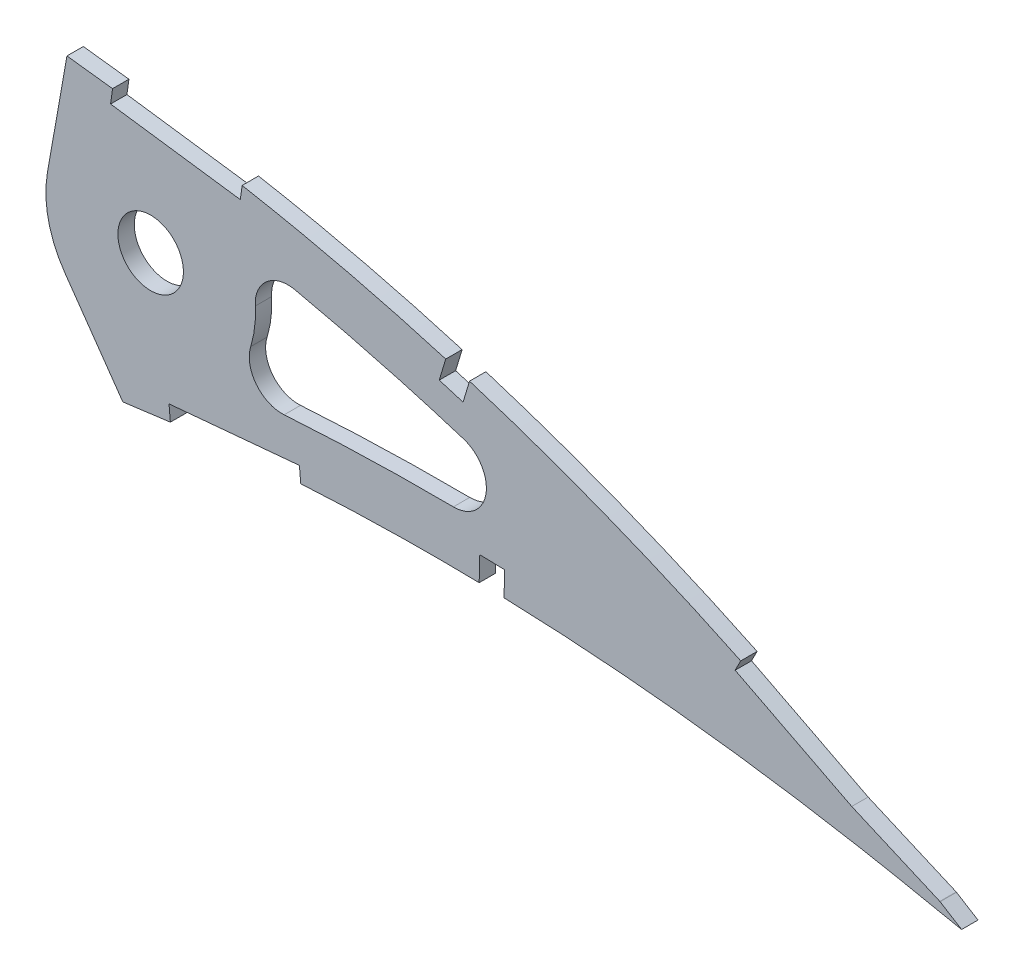
SolidWorks part; units mm, degrees
material "Plywood"
ref_plane "Front Plane" through (0, 0, 0) normal (0, 0, 1) x (1, 0, 0)
ref_plane "Top Plane" through (0, 0, 0) normal (0, 1, 0) x (1, 0, 0)
ref_plane "Right Plane" through (0, 0, 0) normal (1, 0, 0) x (0, 0, -1)
curve "Curve2"
  spline degree 3 poles (520.229, 0.8111, 0) (520.1892, 0.8357, 0) (520.0299, 0.9341, 0) (519.6711, 1.1542, 0) (519.0735, 1.5208, 0) (518.237, 2.0313, 0) (517.1622, 2.6844, 0) (515.8486, 3.4756, 0) (514.2969, 4.4021, 0) (512.5075, 5.4598, 0) (510.4807, 6.6436, 0) (508.2172, 7.9486, 0) (505.7172, 9.3676, 0) (502.9816, 10.8948, 0) (500.0114, 12.5227, 0) (496.8072, 14.2443, 0) (493.3701, 16.0505, 0) (489.7015, 17.9338, 0) (485.8019, 19.8836, 0) (481.6733, 21.8919, 0) (477.317, 23.9487, 0) (472.7345, 26.0429, 0) (467.9284, 28.1661, 0) (462.9001, 30.305, 0) (457.6524, 32.4505, 0) (452.1876, 34.5902, 0) (446.5089, 36.7144, 0) (440.6184, 38.8094, 0) (434.5207, 40.866, 0) (428.2186, 42.8708, 0) (421.7166, 44.813, 0) (415.0186, 46.68, 0) (408.1302, 48.4622, 0) (401.0555, 50.1466, 0) (393.8008, 51.7219, 0) (386.3718, 53.1787, 0) (378.7746, 54.5024, 0) (371.0303, 55.692, 0) (363.2636, 56.6815, 0) (355.5128, 57.652, 0) (347.7736, 58.5637, 0) (339.9398, 59.4368, 0) (332.019, 60.2663, 0) (324.019, 61.0497, 0) (315.9478, 61.7836, 0) (307.814, 62.4658, 0) (299.6253, 63.0925, 0) (291.3904, 63.6628, 0) (283.1174, 64.1714, 0) (274.8152, 64.6183, 0) (266.4922, 65.0001, 0) (258.157, 65.3142, 0) (249.8185, 65.5589, 0) (241.4854, 65.7316, 0) (233.1666, 65.8314, 0) (224.8708, 65.8555, 0) (216.6071, 65.8035, 0) (208.384, 65.6736, 0) (200.2107, 65.464, 0) (192.0958, 65.1743, 0) (184.048, 64.8046, 0) (176.0762, 64.3519, 0) (168.189, 63.8191, 0) (160.3952, 63.2038, 0) (152.7034, 62.506, 0) (145.1216, 61.7286, 0) (137.6583, 60.8693, 0) (130.3214, 59.9308, 0) (123.1191, 58.9147, 0) (116.0593, 57.8206, 0) (109.1496, 56.6517, 0) (102.3976, 55.409, 0) (95.8102, 54.0963, 0) (89.3948, 52.714, 0) (83.1581, 51.266, 0) (77.1065, 49.7551, 0) (71.2467, 48.1838, 0) (65.5845, 46.5561, 0) (60.1256, 44.8756, 0) (54.8764, 43.1442, 0) (49.8409, 41.3683, 0) (45.0253, 39.5493, 0) (40.4333, 37.6928, 0) (36.0702, 35.8014, 0) (31.9393, 33.8806, 0) (28.0452, 31.9329, 0) (24.3908, 29.9636, 0) (20.9797, 27.9757, 0) (17.8153, 25.973, 0) (14.8987, 23.9604, 0) (12.2341, 21.9394, 0) (9.8224, 19.9149, 0) (7.6651, 17.8901, 0) (5.7652, 15.8664, 0) (4.1228, 13.8473, 0) (2.7399, 11.8344, 0) (1.6168, 9.8297, 0) (0.7561, 7.8345, 0) (0.1568, 5.85, 0) (-0.1712, 3.8792, 0) (-0.2528, 1.9205, 0) (-0.0842, 0.6392, 0) (0, 0, 0) knots 0 0 0 0 0.000254 0.001015 0.002283 0.004057 0.006331 0.009105 0.012374 0.016134 0.02038 0.025106 0.030306 0.035972 0.0421 0.048678 0.055702 0.06316 0.071046 0.07935 0.088063 0.097176 0.106678 0.116562 0.126814 0.137428 0.148394 0.1597 0.171338 0.183298 0.19557 0.208144 0.221012 0.234162 0.247587 0.261277 0.275223 0.289414 0.303771 0.317689 0.331784 0.34604 0.360444 0.374983 0.38964 0.404403 0.419257 0.434187 0.449177 0.464215 0.479284 0.49437 0.509458 0.524532 0.539579 0.554583 0.56953 0.584403 0.599191 0.613877 0.628447 0.642889 0.657186 0.671326 0.685294 0.699078 0.712665 0.726043 0.739198 0.752118 0.764792 0.777208 0.789356 0.801224 0.812804 0.824083 0.835055 0.84571 0.856038 0.866034 0.875689 0.884998 0.893953 0.902553 0.910789 0.918661 0.926166 0.933303 0.940071 0.946475 0.952518 0.958205 0.963547 0.968557 0.97325 0.977651 0.981787 0.985694 0.989415 0.993001 0.996508 1 1 1 1
curve "Curve3"
  spline degree 3 poles (0, 0, 0) (0.1336, -0.6306, 0) (0.4014, -1.8948, 0) (1.129, -3.7148, 0) (2.0912, -5.4642, 0) (3.3081, -7.1386, 0) (4.7718, -8.7374, 0) (6.479, -10.2623, 0) (8.428, -11.7125, 0) (10.6162, -13.0874, 0) (13.0406, -14.3883, 0) (15.6982, -15.6145, 0) (18.5868, -16.7656, 0) (21.7032, -17.8401, 0) (25.0435, -18.8396, 0) (28.6046, -19.7616, 0) (32.3825, -20.6074, 0) (36.3735, -21.375, 0) (40.5732, -22.065, 0) (44.9774, -22.6771, 0) (49.5814, -23.2117, 0) (54.3808, -23.6676, 0) (59.3708, -24.0458, 0) (64.5464, -24.3466, 0) (69.9027, -24.5709, 0) (75.4344, -24.718, 0) (81.1363, -24.7899, 0) (87.003, -24.788, 0) (93.0289, -24.7115, 0) (99.2088, -24.5648, 0) (105.5368, -24.3469, 0) (112.0073, -24.0604, 0) (118.6142, -23.7083, 0) (125.3518, -23.2917, 0) (132.2141, -22.8125, 0) (139.1951, -22.2745, 0) (146.2885, -21.679, 0) (153.4882, -21.0296, 0) (160.7876, -20.3295, 0) (168.1806, -19.5808, 0) (175.6606, -18.7872, 0) (183.2209, -17.9512, 0) (190.8551, -17.0772, 0) (198.5563, -16.1668, 0) (206.3179, -15.2253, 0) (214.1326, -14.2544, 0) (221.9939, -13.2579, 0) (229.8947, -12.2404, 0) (237.8276, -11.2019, 0) (245.786, -10.1497, 0) (253.7621, -9.0829, 0) (261.7491, -8.0072, 0) (269.7395, -6.9257, 0) (277.7256, -5.8389, 0) (285.7003, -4.7513, 0) (293.6562, -3.6657, 0) (301.5856, -2.5824, 0) (309.4812, -1.5067, 0) (317.3352, -0.4385, 0) (325.1402, 0.6201, 0) (332.8888, 1.6659, 0) (340.5737, 2.6975, 0) (348.187, 3.7144, 0) (355.721, 4.7168, 0) (363.0553, 5.6745, 0) (370.1707, 6.6383, 0) (377.0913, 7.4284, 0) (383.9258, 8.1028, 0) (390.6811, 8.6557, 0) (397.3493, 9.0951, 0) (403.9227, 9.4241, 0) (410.3934, 9.6473, 0) (416.7532, 9.7713, 0) (422.9943, 9.7993, 0) (429.1081, 9.7402, 0) (435.0867, 9.5987, 0) (440.9216, 9.3813, 0) (446.6049, 9.0952, 0) (452.1283, 8.7483, 0) (457.4837, 8.3456, 0) (462.6634, 7.8966, 0) (467.6597, 7.4078, 0) (472.4647, 6.8849, 0) (477.0715, 6.3387, 0) (481.4727, 5.7729, 0) (485.6616, 5.1968, 0) (489.6316, 4.6162, 0) (493.3764, 4.0385, 0) (496.89, 3.4693, 0) (500.1667, 2.916, 0) (503.2016, 2.384, 0) (505.9892, 1.8782, 0) (508.5257, 1.4052, 0) (510.8062, 0.9673, 0) (512.8275, 0.5717, 0) (514.5859, 0.2202, 0) (516.0789, -0.0824, 0) (517.3037, -0.3347, 0) (518.2586, -0.5328, 0) (518.9417, -0.6767, 0) (519.3522, -0.7624, 0) (519.5346, -0.8013, 0) (519.5802, -0.8111, 0) knots 0 0 0 0 0.003638 0.007293 0.011028 0.014901 0.018963 0.023258 0.027821 0.032679 0.037853 0.043362 0.049215 0.055422 0.061989 0.068918 0.076211 0.083868 0.091887 0.100266 0.109 0.118085 0.127515 0.137285 0.147388 0.157816 0.168563 0.179619 0.190977 0.202627 0.21456 0.226767 0.239236 0.251959 0.264924 0.27812 0.291536 0.30516 0.318981 0.332985 0.347163 0.361499 0.375981 0.390597 0.405333 0.420175 0.43511 0.450124 0.465203 0.480333 0.495501 0.51069 0.525887 0.541078 0.556247 0.571382 0.586466 0.601485 0.616424 0.631269 0.646007 0.660621 0.675098 0.689423 0.703582 0.716908 0.730009 0.742952 0.755726 0.76832 0.780724 0.792927 0.804916 0.816679 0.828204 0.839475 0.850481 0.861208 0.871639 0.881763 0.891564 0.901027 0.910139 0.918884 0.927249 0.935221 0.942785 0.949928 0.956638 0.962904 0.968712 0.974054 0.978918 0.983297 0.98718 0.990561 0.993433 0.995791 0.99763 0.998946 0.999737 1 1 1 1
sketch "Sketch1" plane through (0, 0, 0) normal (0, 0, 1) x (1, 0, 0)
  line L1 (519.5802, -0.8111) -> (524.4049, -1.7687)
  line L2 (520.229, 0.8111) -> (524.4049, -1.7687)
  spline S0 degree 3 poles (-2903.7635, -749.124) (66.2436, 68.8235) (-8.6937, 20.855) (1.129, -3.7148) (2.0912, -5.4642) (3.3081, -7.1386) (4.7718, -8.7374) (6.479, -10.2623) (8.428, -11.7125) (10.6162, -13.0874) (13.0406, -14.3883) (15.6982, -15.6145) (18.5868, -16.7656) (21.7032, -17.8401) (25.0435, -18.8396) (28.6046, -19.7616) (32.3825, -20.6074) (36.3735, -21.375) (40.5732, -22.065) (44.9774, -22.6771) (49.5814, -23.2117) (54.3808, -23.6676) (59.3708, -24.0458) (64.5464, -24.3466) (69.9027, -24.5709) (75.4344, -24.718) (81.1363, -24.7899) (87.003, -24.788) (93.0289, -24.7115) (99.2088, -24.5648) (105.5368, -24.3469) (112.0073, -24.0604) (118.6142, -23.7083) (125.3518, -23.2917) (132.2141, -22.8125) (139.1951, -22.2745) (146.2885, -21.679) (153.4882, -21.0296) (160.7876, -20.3295) (168.1806, -19.5808) (175.6606, -18.7872) (183.2209, -17.9512) (190.8551, -17.0772) (198.5563, -16.1668) (206.3179, -15.2253) (214.1326, -14.2544) (221.9939, -13.2579) (229.8947, -12.2404) (237.8276, -11.2019) (245.786, -10.1497) (253.7621, -9.0829) (261.7491, -8.0072) (269.7395, -6.9257) (277.7256, -5.8389) (285.7003, -4.7513) (293.6562, -3.6657) (301.5856, -2.5824) (309.4812, -1.5067) (317.3352, -0.4385) (325.1402, 0.6201) (332.8888, 1.6659) (340.5737, 2.6975) (348.187, 3.7144) (355.721, 4.7168) (363.0553, 5.6745) (370.1707, 6.6383) (377.0913, 7.4284) (383.9258, 8.1028) (390.6811, 8.6557) (397.3493, 9.0951) (403.9227, 9.4241) (410.3934, 9.6473) (416.7532, 9.7713) (422.9943, 9.7993) (429.1081, 9.7402) (435.0867, 9.5987) (440.9216, 9.3813) (446.6049, 9.0952) (452.1283, 8.7483) (457.4837, 8.3456) (462.6634, 7.8966) (467.6597, 7.4078) (472.4647, 6.8849) (477.0715, 6.3387) (481.4727, 5.7729) (485.6616, 5.1968) (489.6316, 4.6162) (493.3764, 4.0385) (496.89, 3.4693) (500.1667, 2.916) (503.2016, 2.384) (505.9892, 1.8782) (508.5257, 1.4052) (510.8062, 0.9673) (512.8275, 0.5717) (514.5859, 0.2202) (516.0789, -0.0824) (517.3037, -0.3347) (518.2586, -0.5328) (518.9417, -0.6767) (537.0698, -4.4604) (553.3394, -15.9066) (1193.1482, 2921.6684) knots -0.137857 -0.137857 -0.137857 -0.137857 0.003638 0.007293 0.011028 0.014901 0.018963 0.023258 0.027821 0.032679 0.037853 0.043362 0.049215 0.055422 0.061989 0.068918 0.076211 0.083868 0.091887 0.100266 0.109 0.118085 0.127515 0.137285 0.147388 0.157816 0.168563 0.179619 0.190977 0.202627 0.21456 0.226767 0.239236 0.251959 0.264924 0.27812 0.291536 0.30516 0.318981 0.332985 0.347163 0.361499 0.375981 0.390597 0.405333 0.420175 0.43511 0.450124 0.465203 0.480333 0.495501 0.51069 0.525887 0.541078 0.556247 0.571382 0.586466 0.601485 0.616424 0.631269 0.646007 0.660621 0.675098 0.689423 0.703582 0.716908 0.730009 0.742952 0.755726 0.76832 0.780724 0.792927 0.804916 0.816679 0.828204 0.839475 0.850481 0.861208 0.871639 0.881763 0.891564 0.901027 0.910139 0.918884 0.927249 0.935221 0.942785 0.949928 0.956638 0.962904 0.968712 0.974054 0.978918 0.983297 0.98718 0.990561 0.993433 0.995791 0.99763 0.998946 0.999737 1.102307 1.102307 1.102307 1.102307 only from (0, 0) to (519.5802, -0.8111) construction
  spline S1 degree 3 poles (2144.5607, 2521.6799) (550.9976, -26.3511) (537.2872, -9.6513) (519.6711, 1.1542) (519.0735, 1.5208) (518.237, 2.0313) (517.1622, 2.6844) (515.8486, 3.4756) (514.2969, 4.4021) (512.5075, 5.4598) (510.4807, 6.6436) (508.2172, 7.9486) (505.7172, 9.3676) (502.9816, 10.8948) (500.0114, 12.5227) (496.8072, 14.2443) (493.3701, 16.0505) (489.7015, 17.9338) (485.8019, 19.8836) (481.6733, 21.8919) (477.317, 23.9487) (472.7345, 26.0429) (467.9284, 28.1661) (462.9001, 30.305) (457.6524, 32.4505) (452.1876, 34.5902) (446.5089, 36.7144) (440.6184, 38.8094) (434.5207, 40.866) (428.2186, 42.8708) (421.7166, 44.813) (415.0186, 46.68) (408.1302, 48.4622) (401.0555, 50.1466) (393.8008, 51.7219) (386.3718, 53.1787) (378.7746, 54.5024) (371.0303, 55.692) (363.2636, 56.6815) (355.5128, 57.652) (347.7736, 58.5637) (339.9398, 59.4368) (332.019, 60.2663) (324.019, 61.0497) (315.9478, 61.7836) (307.814, 62.4658) (299.6253, 63.0925) (291.3904, 63.6628) (283.1174, 64.1714) (274.8152, 64.6183) (266.4922, 65.0001) (258.157, 65.3142) (249.8185, 65.5589) (241.4854, 65.7316) (233.1666, 65.8314) (224.8708, 65.8555) (216.6071, 65.8035) (208.384, 65.6736) (200.2107, 65.464) (192.0958, 65.1743) (184.048, 64.8046) (176.0762, 64.3519) (168.189, 63.8191) (160.3952, 63.2038) (152.7034, 62.506) (145.1216, 61.7286) (137.6583, 60.8693) (130.3214, 59.9308) (123.1191, 58.9147) (116.0593, 57.8206) (109.1496, 56.6517) (102.3976, 55.409) (95.8102, 54.0963) (89.3948, 52.714) (83.1581, 51.266) (77.1065, 49.7551) (71.2467, 48.1838) (65.5845, 46.5561) (60.1256, 44.8756) (54.8764, 43.1442) (49.8409, 41.3683) (45.0253, 39.5493) (40.4333, 37.6928) (36.0702, 35.8014) (31.9393, 33.8806) (28.0452, 31.9329) (24.3908, 29.9636) (20.9797, 27.9757) (17.8153, 25.973) (14.8987, 23.9604) (12.2341, 21.9394) (9.8224, 19.9149) (7.6651, 17.8901) (5.7652, 15.8664) (4.1228, 13.8473) (2.7399, 11.8344) (1.6168, 9.8297) (0.7561, 7.8345) (0.1568, 5.85) (-0.1712, 3.8792) (-1.2714, -22.5145) (85.5395, -42.7616) (-2987.8188, -259.5241) knots -0.109813 -0.109813 -0.109813 -0.109813 0.000254 0.001015 0.002283 0.004057 0.006331 0.009105 0.012374 0.016134 0.02038 0.025106 0.030306 0.035972 0.0421 0.048678 0.055702 0.06316 0.071046 0.07935 0.088063 0.097176 0.106678 0.116562 0.126814 0.137428 0.148394 0.1597 0.171338 0.183298 0.19557 0.208144 0.221012 0.234162 0.247587 0.261277 0.275223 0.289414 0.303771 0.317689 0.331784 0.34604 0.360444 0.374983 0.38964 0.404403 0.419257 0.434187 0.449177 0.464215 0.479284 0.49437 0.509458 0.524532 0.539579 0.554583 0.56953 0.584403 0.599191 0.613877 0.628447 0.642889 0.657186 0.671326 0.685294 0.699078 0.712665 0.726043 0.739198 0.752118 0.764792 0.777208 0.789356 0.801224 0.812804 0.824083 0.835055 0.84571 0.856038 0.866034 0.875689 0.884998 0.893953 0.902553 0.910789 0.918661 0.926166 0.933303 0.940071 0.946475 0.952518 0.958205 0.963547 0.968557 0.97325 0.977651 0.981787 0.985694 0.989415 0.993001 0.996508 1.132043 1.132043 1.132043 1.132043 only from (520.229, 0.8111) to (0, 0) construction
  spline S2 degree 3 poles (0, 0) (0.1336, -0.6306) (0.4014, -1.8948) (1.129, -3.7148) (2.0912, -5.4642) (3.3081, -7.1386) (4.7718, -8.7374) (6.479, -10.2623) (8.428, -11.7125) (10.6162, -13.0874) (13.0406, -14.3883) (15.6982, -15.6145) (18.5868, -16.7656) (21.7032, -17.8401) (25.0435, -18.8396) (28.6046, -19.7616) (32.3825, -20.6074) (36.3735, -21.375) (40.5732, -22.065) (44.9774, -22.6771) (49.5814, -23.2117) (54.3808, -23.6676) (59.3708, -24.0458) (64.5464, -24.3466) (69.9027, -24.5709) (75.4344, -24.718) (81.1363, -24.7899) (87.003, -24.788) (93.0289, -24.7115) (99.2088, -24.5648) (105.5368, -24.3469) (112.0073, -24.0604) (118.6142, -23.7083) (125.3518, -23.2917) (132.2141, -22.8125) (139.1951, -22.2745) (146.2885, -21.679) (153.4882, -21.0296) (160.7876, -20.3295) (168.1806, -19.5808) (175.6606, -18.7872) (183.2209, -17.9512) (190.8551, -17.0772) (198.5563, -16.1668) (206.3179, -15.2253) (214.1326, -14.2544) (221.9939, -13.2579) (229.8947, -12.2404) (237.8276, -11.2019) (245.786, -10.1497) (253.7621, -9.0829) (261.7491, -8.0072) (269.7395, -6.9257) (277.7256, -5.8389) (285.7003, -4.7513) (293.6562, -3.6657) (301.5856, -2.5824) (309.4812, -1.5067) (317.3352, -0.4385) (325.1402, 0.6201) (332.8888, 1.6659) (340.5737, 2.6975) (348.187, 3.7144) (355.721, 4.7168) (363.0553, 5.6745) (370.1707, 6.6383) (377.0913, 7.4284) (383.9258, 8.1028) (390.6811, 8.6557) (397.3493, 9.0951) (403.9227, 9.4241) (410.3934, 9.6473) (416.7532, 9.7713) (422.9943, 9.7993) (429.1081, 9.7402) (435.0867, 9.5987) (440.9216, 9.3813) (446.6049, 9.0952) (452.1283, 8.7483) (457.4837, 8.3456) (462.6634, 7.8966) (467.6597, 7.4078) (472.4647, 6.8849) (477.0715, 6.3387) (481.4727, 5.7729) (485.6616, 5.1968) (489.6316, 4.6162) (493.3764, 4.0385) (496.89, 3.4693) (500.1667, 2.916) (503.2016, 2.384) (505.9892, 1.8782) (508.5257, 1.4052) (510.8062, 0.9673) (512.8275, 0.5717) (514.5859, 0.2202) (516.0789, -0.0824) (517.3037, -0.3347) (518.2586, -0.5328) (518.9417, -0.6767) (519.3522, -0.7624) (519.5346, -0.8013) (519.5802, -0.8111) knots 0 0 0 0 0.003638 0.007293 0.011028 0.014901 0.018963 0.023258 0.027821 0.032679 0.037853 0.043362 0.049215 0.055422 0.061989 0.068918 0.076211 0.083868 0.091887 0.100266 0.109 0.118085 0.127515 0.137285 0.147388 0.157816 0.168563 0.179619 0.190977 0.202627 0.21456 0.226767 0.239236 0.251959 0.264924 0.27812 0.291536 0.30516 0.318981 0.332985 0.347163 0.361499 0.375981 0.390597 0.405333 0.420175 0.43511 0.450124 0.465203 0.480333 0.495501 0.51069 0.525887 0.541078 0.556247 0.571382 0.586466 0.601485 0.616424 0.631269 0.646007 0.660621 0.675098 0.689423 0.703582 0.716908 0.730009 0.742952 0.755726 0.76832 0.780724 0.792927 0.804916 0.816679 0.828204 0.839475 0.850481 0.861208 0.871639 0.881763 0.891564 0.901027 0.910139 0.918884 0.927249 0.935221 0.942785 0.949928 0.956638 0.962904 0.968712 0.974054 0.978918 0.983297 0.98718 0.990561 0.993433 0.995791 0.99763 0.998946 0.999737 1 1 1 1
  spline S3 degree 3 poles (520.229, 0.8111) (520.1892, 0.8357) (520.0299, 0.9341) (519.6711, 1.1542) (519.0735, 1.5208) (518.237, 2.0313) (517.1622, 2.6844) (515.8486, 3.4756) (514.2969, 4.4021) (512.5075, 5.4598) (510.4807, 6.6436) (508.2172, 7.9486) (505.7172, 9.3676) (502.9816, 10.8948) (500.0114, 12.5227) (496.8072, 14.2443) (493.3701, 16.0505) (489.7015, 17.9338) (485.8019, 19.8836) (481.6733, 21.8919) (477.317, 23.9487) (472.7345, 26.0429) (467.9284, 28.1661) (462.9001, 30.305) (457.6524, 32.4505) (452.1876, 34.5902) (446.5089, 36.7144) (440.6184, 38.8094) (434.5207, 40.866) (428.2186, 42.8708) (421.7166, 44.813) (415.0186, 46.68) (408.1302, 48.4622) (401.0555, 50.1466) (393.8008, 51.7219) (386.3718, 53.1787) (378.7746, 54.5024) (371.0303, 55.692) (363.2636, 56.6815) (355.5128, 57.652) (347.7736, 58.5637) (339.9398, 59.4368) (332.019, 60.2663) (324.019, 61.0497) (315.9478, 61.7836) (307.814, 62.4658) (299.6253, 63.0925) (291.3904, 63.6628) (283.1174, 64.1714) (274.8152, 64.6183) (266.4922, 65.0001) (258.157, 65.3142) (249.8185, 65.5589) (241.4854, 65.7316) (233.1666, 65.8314) (224.8708, 65.8555) (216.6071, 65.8035) (208.384, 65.6736) (200.2107, 65.464) (192.0958, 65.1743) (184.048, 64.8046) (176.0762, 64.3519) (168.189, 63.8191) (160.3952, 63.2038) (152.7034, 62.506) (145.1216, 61.7286) (137.6583, 60.8693) (130.3214, 59.9308) (123.1191, 58.9147) (116.0593, 57.8206) (109.1496, 56.6517) (102.3976, 55.409) (95.8102, 54.0963) (89.3948, 52.714) (83.1581, 51.266) (77.1065, 49.7551) (71.2467, 48.1838) (65.5845, 46.5561) (60.1256, 44.8756) (54.8764, 43.1442) (49.8409, 41.3683) (45.0253, 39.5493) (40.4333, 37.6928) (36.0702, 35.8014) (31.9393, 33.8806) (28.0452, 31.9329) (24.3908, 29.9636) (20.9797, 27.9757) (17.8153, 25.973) (14.8987, 23.9604) (12.2341, 21.9394) (9.8224, 19.9149) (7.6651, 17.8901) (5.7652, 15.8664) (4.1228, 13.8473) (2.7399, 11.8344) (1.6168, 9.8297) (0.7561, 7.8345) (0.1568, 5.85) (-0.1712, 3.8792) (-0.2528, 1.9205) (-0.0842, 0.6392) (0, 0) knots 0 0 0 0 0.000254 0.001015 0.002283 0.004057 0.006331 0.009105 0.012374 0.016134 0.02038 0.025106 0.030306 0.035972 0.0421 0.048678 0.055702 0.06316 0.071046 0.07935 0.088063 0.097176 0.106678 0.116562 0.126814 0.137428 0.148394 0.1597 0.171338 0.183298 0.19557 0.208144 0.221012 0.234162 0.247587 0.261277 0.275223 0.289414 0.303771 0.317689 0.331784 0.34604 0.360444 0.374983 0.38964 0.404403 0.419257 0.434187 0.449177 0.464215 0.479284 0.49437 0.509458 0.524532 0.539579 0.554583 0.56953 0.584403 0.599191 0.613877 0.628447 0.642889 0.657186 0.671326 0.685294 0.699078 0.712665 0.726043 0.739198 0.752118 0.764792 0.777208 0.789356 0.801224 0.812804 0.824083 0.835055 0.84571 0.856038 0.866034 0.875689 0.884998 0.893953 0.902553 0.910789 0.918661 0.926166 0.933303 0.940071 0.946475 0.952518 0.958205 0.963547 0.968557 0.97325 0.977651 0.981787 0.985694 0.989415 0.993001 0.996508 1 1 1 1
extrude "Boss-Extrude1" add sketch "Sketch1" along normal blind 3.175
sketch "Sketch4" plane through (0, 0, 0) normal (0, 0, -1) x (-1, 0, 0)
  line L0 (-347.1309, 36.7611) -> (-350.9097, 58.1919)
  line L1 (-350.497, 21.5775) -> (-361.7496, 5.5072)
  line L2 (-520.229, 0.8111) -> (-524.4049, -1.7687)
  line L3 (-524.4049, -1.7687) -> (-519.5802, -0.8111)
  line L6 (-367.1422, 33.2326) -> (-394.958, 33.2326)
  circle A0 centre (-367.1422, 33.2326) radius 20.32
  circle A1 centre (-367.1422, 33.2326) radius 6.35
  spline S0 degree 1 poles (-521.6997, 9.1254) (-10.022, 1.7185) knots 0 0 1 1 construction
  spline S1 degree 1 poles (-10.022, 1.7185) (-514.8893, -7.8326) knots 0 0 1 1 construction
  spline S2 degree 3 poles (2987.4901, -259.5009) (-85.5334, -42.7602) (1.2713, -22.5136) (0.1712, 3.8792) (-0.1568, 5.85) (-0.7561, 7.8345) (-1.6168, 9.8297) (-2.7399, 11.8344) (-4.1228, 13.8473) (-5.7652, 15.8664) (-7.6651, 17.8901) (-9.8224, 19.9149) (-12.2341, 21.9394) (-14.8987, 23.9604) (-17.8153, 25.973) (-20.9797, 27.9757) (-24.3908, 29.9636) (-28.0452, 31.9329) (-31.9393, 33.8806) (-36.0702, 35.8014) (-40.4333, 37.6928) (-45.0253, 39.5493) (-49.8409, 41.3683) (-54.8764, 43.1442) (-60.1256, 44.8756) (-65.5845, 46.5561) (-71.2467, 48.1838) (-77.1065, 49.7551) (-83.1581, 51.266) (-89.3948, 52.714) (-95.8102, 54.0963) (-102.3976, 55.409) (-109.1496, 56.6517) (-116.0593, 57.8206) (-123.1191, 58.9147) (-130.3214, 59.9308) (-137.6583, 60.8693) (-145.1216, 61.7286) (-152.7034, 62.506) (-160.3952, 63.2038) (-168.189, 63.8191) (-176.0762, 64.3519) (-184.048, 64.8046) (-192.0958, 65.1743) (-200.2107, 65.464) (-208.384, 65.6736) (-216.6071, 65.8035) (-224.8708, 65.8555) (-233.1666, 65.8314) (-241.4854, 65.7316) (-249.8185, 65.5589) (-258.157, 65.3142) (-266.4922, 65.0001) (-274.8152, 64.6183) (-283.1174, 64.1714) (-291.3904, 63.6628) (-299.6253, 63.0925) (-307.814, 62.4658) (-315.9478, 61.7836) (-324.019, 61.0497) (-332.019, 60.2663) (-339.9398, 59.4368) (-347.7736, 58.5637) (-355.5128, 57.652) (-363.2636, 56.6815) (-371.0303, 55.692) (-378.7746, 54.5024) (-386.3718, 53.1787) (-393.8008, 51.7219) (-401.0555, 50.1466) (-408.1302, 48.4622) (-415.0186, 46.68) (-421.7166, 44.813) (-428.2186, 42.8708) (-434.5207, 40.866) (-440.6184, 38.8094) (-446.5089, 36.7144) (-452.1876, 34.5902) (-457.6524, 32.4505) (-462.9001, 30.305) (-467.9284, 28.1661) (-472.7345, 26.0429) (-477.317, 23.9487) (-481.6733, 21.8919) (-485.8019, 19.8836) (-489.7015, 17.9338) (-493.3701, 16.0505) (-496.8072, 14.2443) (-500.0114, 12.5227) (-502.9816, 10.8948) (-505.7172, 9.3676) (-508.2172, 7.9486) (-510.4807, 6.6436) (-512.5075, 5.4598) (-514.2969, 4.4021) (-515.8486, 3.4756) (-517.1622, 2.6844) (-518.237, 2.0313) (-519.0735, 1.5208) (-519.6711, 1.1542) (-537.2876, -9.6516) (-550.9983, -26.352) (-2144.6851, 2521.8788) knots -0.132038 -0.132038 -0.132038 -0.132038 0.003492 0.006999 0.010585 0.014306 0.018213 0.022349 0.02675 0.031443 0.036453 0.041795 0.047482 0.053525 0.059929 0.066697 0.073834 0.081339 0.089211 0.097447 0.106047 0.115002 0.124311 0.133966 0.143962 0.15429 0.164945 0.175917 0.187196 0.198776 0.210644 0.222792 0.235208 0.247882 0.260802 0.273957 0.287335 0.300922 0.314706 0.328674 0.342814 0.357111 0.371553 0.386123 0.400809 0.415597 0.43047 0.445417 0.460421 0.475468 0.490542 0.50563 0.520716 0.535785 0.550823 0.565813 0.580743 0.595597 0.61036 0.625017 0.639556 0.65396 0.668216 0.682311 0.696229 0.710586 0.724777 0.738723 0.752413 0.765838 0.778988 0.791856 0.80443 0.816702 0.828662 0.8403 0.851606 0.862572 0.873186 0.883438 0.893322 0.902824 0.911937 0.92065 0.928954 0.93684 0.944298 0.951322 0.9579 0.964028 0.969694 0.974894 0.97962 0.983866 0.987626 0.990895 0.993669 0.995943 0.997717 0.998985 0.999746 1.109816 1.109816 1.109816 1.109816 only from (0, 0) to (-520.229, 0.8111)
  spline S3 degree 3 poles (-1193.1472, 2921.6638) (-553.3393, -15.9066) (-537.0698, -4.4604) (-518.9417, -0.6767) (-518.2586, -0.5328) (-517.3037, -0.3347) (-516.0789, -0.0824) (-514.5859, 0.2202) (-512.8275, 0.5717) (-510.8062, 0.9673) (-508.5257, 1.4052) (-505.9892, 1.8782) (-503.2016, 2.384) (-500.1667, 2.916) (-496.89, 3.4693) (-493.3764, 4.0385) (-489.6316, 4.6162) (-485.6616, 5.1968) (-481.4727, 5.7729) (-477.0715, 6.3387) (-472.4647, 6.8849) (-467.6597, 7.4078) (-462.6634, 7.8966) (-457.4837, 8.3456) (-452.1283, 8.7483) (-446.6049, 9.0952) (-440.9216, 9.3813) (-435.0867, 9.5987) (-429.1081, 9.7402) (-422.9943, 9.7993) (-416.7532, 9.7713) (-410.3934, 9.6473) (-403.9227, 9.4241) (-397.3493, 9.0951) (-390.6811, 8.6557) (-383.9258, 8.1028) (-377.0913, 7.4284) (-370.1707, 6.6383) (-363.0553, 5.6745) (-355.721, 4.7168) (-348.187, 3.7144) (-340.5737, 2.6975) (-332.8888, 1.6659) (-325.1402, 0.6201) (-317.3352, -0.4385) (-309.4812, -1.5067) (-301.5856, -2.5824) (-293.6562, -3.6657) (-285.7003, -4.7513) (-277.7256, -5.8389) (-269.7395, -6.9257) (-261.7491, -8.0072) (-253.7621, -9.0829) (-245.786, -10.1497) (-237.8276, -11.2019) (-229.8947, -12.2404) (-221.9939, -13.2579) (-214.1326, -14.2544) (-206.3179, -15.2253) (-198.5563, -16.1668) (-190.8551, -17.0772) (-183.2209, -17.9512) (-175.6606, -18.7872) (-168.1806, -19.5808) (-160.7876, -20.3295) (-153.4882, -21.0296) (-146.2885, -21.679) (-139.1951, -22.2745) (-132.2141, -22.8125) (-125.3518, -23.2917) (-118.6142, -23.7083) (-112.0073, -24.0604) (-105.5368, -24.3469) (-99.2088, -24.5648) (-93.0289, -24.7115) (-87.003, -24.788) (-81.1363, -24.7899) (-75.4344, -24.718) (-69.9027, -24.5709) (-64.5464, -24.3466) (-59.3708, -24.0458) (-54.3808, -23.6676) (-49.5814, -23.2117) (-44.9774, -22.6771) (-40.5732, -22.065) (-36.3735, -21.375) (-32.3825, -20.6074) (-28.6046, -19.7616) (-25.0435, -18.8396) (-21.7032, -17.8401) (-18.5868, -16.7656) (-15.6982, -15.6145) (-13.0406, -14.3883) (-10.6162, -13.0874) (-8.428, -11.7125) (-6.479, -10.2623) (-4.7718, -8.7374) (-3.3081, -7.1386) (-2.0912, -5.4642) (-1.129, -3.7148) (8.6936, 20.8547) (-66.2416, 68.8223) (2903.6435, -749.0909) knots -0.102307 -0.102307 -0.102307 -0.102307 0.000263 0.001054 0.00237 0.004209 0.006567 0.009439 0.01282 0.016703 0.021082 0.025946 0.031288 0.037096 0.043362 0.050072 0.057215 0.064779 0.072751 0.081116 0.089861 0.098973 0.108436 0.118237 0.128361 0.138792 0.149519 0.160525 0.171796 0.183321 0.195084 0.207073 0.219276 0.23168 0.244274 0.257048 0.269991 0.283092 0.296418 0.310577 0.324902 0.339379 0.353993 0.368731 0.383576 0.398515 0.413534 0.428618 0.443753 0.458922 0.474113 0.48931 0.504499 0.519667 0.534797 0.549876 0.56489 0.579825 0.594667 0.609403 0.624019 0.638501 0.652837 0.667015 0.681019 0.69484 0.708464 0.72188 0.735076 0.748041 0.760764 0.773233 0.78544 0.797373 0.809023 0.820381 0.831437 0.842184 0.852612 0.862715 0.872485 0.881915 0.891 0.899734 0.908113 0.916132 0.923789 0.931082 0.938011 0.944578 0.950785 0.956638 0.962147 0.967321 0.972179 0.976742 0.981037 0.985099 0.988972 0.992707 0.996362 1.137855 1.137855 1.137855 1.137855 only from (-519.5802, -0.8111) to (0, 0)
  spline S4 degree 3 poles (0, 0) (0.0842, 0.6392) (0.2528, 1.9205) (0.1712, 3.8792) (-0.1568, 5.85) (-0.7561, 7.8345) (-1.6168, 9.8297) (-2.7399, 11.8344) (-4.1228, 13.8473) (-5.7652, 15.8664) (-7.6651, 17.8901) (-9.8224, 19.9149) (-12.2341, 21.9394) (-14.8987, 23.9604) (-17.8153, 25.973) (-20.9797, 27.9757) (-24.3908, 29.9636) (-28.0452, 31.9329) (-31.9393, 33.8806) (-36.0702, 35.8014) (-40.4333, 37.6928) (-45.0253, 39.5493) (-49.8409, 41.3683) (-54.8764, 43.1442) (-60.1256, 44.8756) (-65.5845, 46.5561) (-71.2467, 48.1838) (-77.1065, 49.7551) (-83.1581, 51.266) (-89.3948, 52.714) (-95.8102, 54.0963) (-102.3976, 55.409) (-109.1496, 56.6517) (-116.0593, 57.8206) (-123.1191, 58.9147) (-130.3214, 59.9308) (-137.6583, 60.8693) (-145.1216, 61.7286) (-152.7034, 62.506) (-160.3952, 63.2038) (-168.189, 63.8191) (-176.0762, 64.3519) (-184.048, 64.8046) (-192.0958, 65.1743) (-200.2107, 65.464) (-208.384, 65.6736) (-216.6071, 65.8035) (-224.8708, 65.8555) (-233.1666, 65.8314) (-241.4854, 65.7316) (-249.8185, 65.5589) (-258.157, 65.3142) (-266.4922, 65.0001) (-274.8152, 64.6183) (-283.1174, 64.1714) (-291.3904, 63.6628) (-299.6253, 63.0925) (-307.814, 62.4658) (-315.9478, 61.7836) (-324.019, 61.0497) (-332.019, 60.2663) (-339.9398, 59.4368) (-347.7736, 58.5637) (-355.5128, 57.652) (-363.2636, 56.6815) (-371.0303, 55.692) (-378.7746, 54.5024) (-386.3718, 53.1787) (-393.8008, 51.7219) (-401.0555, 50.1466) (-408.1302, 48.4622) (-415.0186, 46.68) (-421.7166, 44.813) (-428.2186, 42.8708) (-434.5207, 40.866) (-440.6184, 38.8094) (-446.5089, 36.7144) (-452.1876, 34.5902) (-457.6524, 32.4505) (-462.9001, 30.305) (-467.9284, 28.1661) (-472.7345, 26.0429) (-477.317, 23.9487) (-481.6733, 21.8919) (-485.8019, 19.8836) (-489.7015, 17.9338) (-493.3701, 16.0505) (-496.8072, 14.2443) (-500.0114, 12.5227) (-502.9816, 10.8948) (-505.7172, 9.3676) (-508.2172, 7.9486) (-510.4807, 6.6436) (-512.5075, 5.4598) (-514.2969, 4.4021) (-515.8486, 3.4756) (-517.1622, 2.6844) (-518.237, 2.0313) (-519.0735, 1.5208) (-519.6711, 1.1542) (-520.0299, 0.9341) (-520.1892, 0.8357) (-520.229, 0.8111) knots 0 0 0 0 0.003492 0.006999 0.010585 0.014306 0.018213 0.022349 0.02675 0.031443 0.036453 0.041795 0.047482 0.053525 0.059929 0.066697 0.073834 0.081339 0.089211 0.097447 0.106047 0.115002 0.124311 0.133966 0.143962 0.15429 0.164945 0.175917 0.187196 0.198776 0.210644 0.222792 0.235208 0.247882 0.260802 0.273957 0.287335 0.300922 0.314706 0.328674 0.342814 0.357111 0.371553 0.386123 0.400809 0.415597 0.43047 0.445417 0.460421 0.475468 0.490542 0.50563 0.520716 0.535785 0.550823 0.565813 0.580743 0.595597 0.61036 0.625017 0.639556 0.65396 0.668216 0.682311 0.696229 0.710586 0.724777 0.738723 0.752413 0.765838 0.778988 0.791856 0.80443 0.816702 0.828662 0.8403 0.851606 0.862572 0.873186 0.883438 0.893322 0.902824 0.911937 0.92065 0.928954 0.93684 0.944298 0.951322 0.9579 0.964028 0.969694 0.974894 0.97962 0.983866 0.987626 0.990895 0.993669 0.995943 0.997717 0.998985 0.999746 1 1 1 1
  spline S5 degree 3 poles (-519.5802, -0.8111) (-519.5346, -0.8013) (-519.3522, -0.7624) (-518.9417, -0.6767) (-518.2586, -0.5328) (-517.3037, -0.3347) (-516.0789, -0.0824) (-514.5859, 0.2202) (-512.8275, 0.5717) (-510.8062, 0.9673) (-508.5257, 1.4052) (-505.9892, 1.8782) (-503.2016, 2.384) (-500.1667, 2.916) (-496.89, 3.4693) (-493.3764, 4.0385) (-489.6316, 4.6162) (-485.6616, 5.1968) (-481.4727, 5.7729) (-477.0715, 6.3387) (-472.4647, 6.8849) (-467.6597, 7.4078) (-462.6634, 7.8966) (-457.4837, 8.3456) (-452.1283, 8.7483) (-446.6049, 9.0952) (-440.9216, 9.3813) (-435.0867, 9.5987) (-429.1081, 9.7402) (-422.9943, 9.7993) (-416.7532, 9.7713) (-410.3934, 9.6473) (-403.9227, 9.4241) (-397.3493, 9.0951) (-390.6811, 8.6557) (-383.9258, 8.1028) (-377.0913, 7.4284) (-370.1707, 6.6383) (-363.0553, 5.6745) (-355.721, 4.7168) (-348.187, 3.7144) (-340.5737, 2.6975) (-332.8888, 1.6659) (-325.1402, 0.6201) (-317.3352, -0.4385) (-309.4812, -1.5067) (-301.5856, -2.5824) (-293.6562, -3.6657) (-285.7003, -4.7513) (-277.7256, -5.8389) (-269.7395, -6.9257) (-261.7491, -8.0072) (-253.7621, -9.0829) (-245.786, -10.1497) (-237.8276, -11.2019) (-229.8947, -12.2404) (-221.9939, -13.2579) (-214.1326, -14.2544) (-206.3179, -15.2253) (-198.5563, -16.1668) (-190.8551, -17.0772) (-183.2209, -17.9512) (-175.6606, -18.7872) (-168.1806, -19.5808) (-160.7876, -20.3295) (-153.4882, -21.0296) (-146.2885, -21.679) (-139.1951, -22.2745) (-132.2141, -22.8125) (-125.3518, -23.2917) (-118.6142, -23.7083) (-112.0073, -24.0604) (-105.5368, -24.3469) (-99.2088, -24.5648) (-93.0289, -24.7115) (-87.003, -24.788) (-81.1363, -24.7899) (-75.4344, -24.718) (-69.9027, -24.5709) (-64.5464, -24.3466) (-59.3708, -24.0458) (-54.3808, -23.6676) (-49.5814, -23.2117) (-44.9774, -22.6771) (-40.5732, -22.065) (-36.3735, -21.375) (-32.3825, -20.6074) (-28.6046, -19.7616) (-25.0435, -18.8396) (-21.7032, -17.8401) (-18.5868, -16.7656) (-15.6982, -15.6145) (-13.0406, -14.3883) (-10.6162, -13.0874) (-8.428, -11.7125) (-6.479, -10.2623) (-4.7718, -8.7374) (-3.3081, -7.1386) (-2.0912, -5.4642) (-1.129, -3.7148) (-0.4014, -1.8948) (-0.1336, -0.6306) (0, 0) knots 0 0 0 0 0.000263 0.001054 0.00237 0.004209 0.006567 0.009439 0.01282 0.016703 0.021082 0.025946 0.031288 0.037096 0.043362 0.050072 0.057215 0.064779 0.072751 0.081116 0.089861 0.098973 0.108436 0.118237 0.128361 0.138792 0.149519 0.160525 0.171796 0.183321 0.195084 0.207073 0.219276 0.23168 0.244274 0.257048 0.269991 0.283092 0.296418 0.310577 0.324902 0.339379 0.353993 0.368731 0.383576 0.398515 0.413534 0.428618 0.443753 0.458922 0.474113 0.48931 0.504499 0.519667 0.534797 0.549876 0.56489 0.579825 0.594667 0.609403 0.624019 0.638501 0.652837 0.667015 0.681019 0.69484 0.708464 0.72188 0.735076 0.748041 0.760764 0.773233 0.78544 0.797373 0.809023 0.820381 0.831437 0.842184 0.852612 0.862715 0.872485 0.881915 0.891 0.899734 0.908113 0.916132 0.923789 0.931082 0.938011 0.944578 0.950785 0.956638 0.962147 0.967321 0.972179 0.976742 0.981037 0.985099 0.988972 0.992707 0.996362 1 1 1 1
  spline S6 degree 3 poles (-521.6997, 9.1254) (-521.5185, 9.1641) (-521.1414, 9.2431) (-520.5013, 9.3777) (-519.6014, 9.5652) (-518.5867, 9.7745) (-516.5017, 10.2002) (-512.0338, 11.0895) (-502.3328, 12.9034) (-482.8666, 16.0553) (-454.7955, 19.1487) (-426.5367, 20.1772) (-403.9091, 19.6864) (-389.7949, 18.8264) (-379.9243, 17.9283) (-374.3105, 17.3355) (-370.0824, 16.8486) (-365.8505, 16.3062) (-361.7465, 15.7537) (-357.6653, 15.2168) (-352.1695, 14.4949) (-345.3171, 13.5814) (-334.359, 12.1168) (-315.179, 9.5288) (-287.8082, 5.789) (-254.9835, 1.3131) (-222.1895, -3.0348) (-189.4106, -7.0959) (-156.654, -10.6508) (-129.3813, -12.9449) (-107.6083, -14.1485) (-91.3205, -14.6521) (-75.1074, -14.6475) (-61.7108, -14.0897) (-51.1341, -13.1896) (-43.3067, -12.2396) (-35.6411, -10.9589) (-28.237, -9.2636) (-21.2892, -7.0583) (-16.2032, -4.6866) (-13.0461, -2.5478) (-11.6056, -1.201) (-10.836, -0.2227) (-10.5202, 0.2936) (-10.2886, 0.7695) (-10.2055, 0.9824) (-10.1785, 1.0643) (-10.1577, 1.1349) (-10.1105, 1.3225) (-10.0643, 1.5249) (-10.0354, 1.6565) (-10.022, 1.7185) knots 0 0 0 0 0.000976 0.001952 0.003903 0.005855 0.007806 0.015612 0.031224 0.062448 0.124896 0.187344 0.218569 0.249793 0.265405 0.273211 0.281017 0.288823 0.296629 0.304435 0.312241 0.327853 0.343465 0.374689 0.437137 0.499585 0.562033 0.624482 0.68693 0.749378 0.780602 0.811826 0.84305 0.874274 0.889886 0.905498 0.92111 0.936722 0.952334 0.967946 0.975753 0.983559 0.987462 0.991365 0.993316 0.995268 0.996243 0.997219 0.998195 0.998683 0.999171 0.999171 0.999171 0.999171
  spline S7 degree 3 poles (-10.022, 1.7185) (-10.0137, 1.7838) (-9.9964, 1.9227) (-9.9722, 2.1338) (-9.9548, 2.3267) (-9.9521, 2.385) (-9.9503, 2.4853) (-9.9613, 2.7344) (-10.0122, 3.1442) (-10.0839, 3.5102) (-10.2224, 4.0331) (-10.6171, 5.1175) (-11.6184, 6.9252) (-14.1026, 10.0907) (-18.4256, 14.0534) (-24.6526, 18.4028) (-31.4923, 22.3392) (-38.7272, 25.9013) (-46.2345, 29.1355) (-56.5074, 33.06) (-69.7207, 37.3231) (-85.9449, 41.5978) (-102.4194, 45.1568) (-124.6274, 49.0726) (-152.7038, 52.5874) (-186.6719, 55.0054) (-220.784, 55.8886) (-254.9542, 55.4386) (-289.1234, 53.7977) (-317.5664, 51.5306) (-337.4323, 49.5018) (-348.7883, 48.2227) (-357.2614, 47.1962) (-365.8396, 46.1279) (-374.0765, 44.9754) (-382.3862, 43.5815) (-393.3717, 41.4855) (-407.0282, 38.3742) (-428.6204, 32.3912) (-455.0706, 23.0586) (-480.6155, 11.4116) (-497.9507, 2.1395) (-506.4753, -2.765) (-510.6983, -5.2786) (-512.8069, -6.557) (-513.8432, -7.1901) (-514.4641, -7.5709) (-514.7453, -7.7437) (-514.8893, -7.8326) knots 0.000796 0.000796 0.000796 0.000796 0.001284 0.001772 0.002748 0.003724 0.004699 0.006651 0.008603 0.010554 0.012506 0.016409 0.024215 0.032021 0.047634 0.063247 0.078859 0.094472 0.110084 0.125697 0.156922 0.188147 0.219372 0.250597 0.313047 0.375498 0.437948 0.500398 0.562848 0.625299 0.656524 0.672136 0.687749 0.703361 0.718974 0.734587 0.750199 0.781424 0.812649 0.8751 0.93755 0.968775 0.984387 0.992194 0.996097 0.998048 0.999024 1 1 1 1
  spline M11 degree 3 poles (0, 0) (0.0842, 0.6392) (0.2528, 1.9205) (0.1712, 3.8792) (-0.1568, 5.85) (-0.7561, 7.8345) (-1.6168, 9.8297) (-2.7399, 11.8344) (-4.1228, 13.8473) (-5.7652, 15.8664) (-7.6651, 17.8901) (-9.8224, 19.9149) (-12.2341, 21.9394) (-14.8987, 23.9604) (-17.8153, 25.973) (-20.9797, 27.9757) (-24.3908, 29.9636) (-28.0452, 31.9329) (-31.9393, 33.8806) (-36.0702, 35.8014) (-40.4333, 37.6928) (-45.0253, 39.5493) (-49.8409, 41.3683) (-54.8764, 43.1442) (-60.1256, 44.8756) (-65.5845, 46.5561) (-71.2467, 48.1838) (-77.1065, 49.7551) (-83.1581, 51.266) (-89.3948, 52.714) (-95.8102, 54.0963) (-102.3976, 55.409) (-109.1496, 56.6517) (-116.0593, 57.8206) (-123.1191, 58.9147) (-130.3214, 59.9308) (-137.6583, 60.8693) (-145.1216, 61.7286) (-152.7034, 62.506) (-160.3952, 63.2038) (-168.189, 63.8191) (-176.0762, 64.3519) (-184.048, 64.8046) (-192.0958, 65.1743) (-200.2107, 65.464) (-208.384, 65.6736) (-216.6071, 65.8035) (-224.8708, 65.8555) (-233.1666, 65.8314) (-241.4854, 65.7316) (-249.8185, 65.5589) (-258.157, 65.3142) (-266.4922, 65.0001) (-274.8152, 64.6183) (-283.1174, 64.1714) (-291.3904, 63.6628) (-299.6253, 63.0925) (-307.814, 62.4658) (-315.9478, 61.7836) (-324.019, 61.0497) (-332.019, 60.2663) (-339.9398, 59.4368) (-347.7736, 58.5637) (-355.5128, 57.652) (-363.2636, 56.6815) (-371.0303, 55.692) (-378.7746, 54.5024) (-386.3718, 53.1787) (-393.8008, 51.7219) (-401.0555, 50.1466) (-408.1302, 48.4622) (-415.0186, 46.68) (-421.7166, 44.813) (-428.2186, 42.8708) (-434.5207, 40.866) (-440.6184, 38.8094) (-446.5089, 36.7144) (-452.1876, 34.5902) (-457.6524, 32.4505) (-462.9001, 30.305) (-467.9284, 28.1661) (-472.7345, 26.0429) (-477.317, 23.9487) (-481.6733, 21.8919) (-485.8019, 19.8836) (-489.7015, 17.9338) (-493.3701, 16.0505) (-496.8072, 14.2443) (-500.0114, 12.5227) (-502.9816, 10.8948) (-505.7172, 9.3676) (-508.2172, 7.9486) (-510.4807, 6.6436) (-512.5075, 5.4598) (-514.2969, 4.4021) (-515.8486, 3.4756) (-517.1622, 2.6844) (-518.237, 2.0313) (-519.0735, 1.5208) (-519.6711, 1.1542) (-520.0299, 0.9341) (-520.1892, 0.8357) (-520.229, 0.8111) knots 0 0 0 0 0.003492 0.006999 0.010585 0.014306 0.018213 0.022349 0.02675 0.031443 0.036453 0.041795 0.047482 0.053525 0.059929 0.066697 0.073834 0.081339 0.089211 0.097447 0.106047 0.115002 0.124311 0.133966 0.143962 0.15429 0.164945 0.175917 0.187196 0.198776 0.210644 0.222792 0.235208 0.247882 0.260802 0.273957 0.287335 0.300922 0.314706 0.328674 0.342814 0.357111 0.371553 0.386123 0.400809 0.415597 0.43047 0.445417 0.460421 0.475468 0.490542 0.50563 0.520716 0.535785 0.550823 0.565813 0.580743 0.595597 0.61036 0.625017 0.639556 0.65396 0.668216 0.682311 0.696229 0.710586 0.724777 0.738723 0.752413 0.765838 0.778988 0.791856 0.80443 0.816702 0.828662 0.8403 0.851606 0.862572 0.873186 0.883438 0.893322 0.902824 0.911937 0.92065 0.928954 0.93684 0.944298 0.951322 0.9579 0.964028 0.969694 0.974894 0.97962 0.983866 0.987626 0.990895 0.993669 0.995943 0.997717 0.998985 0.999746 1 1 1 1
  spline M14 degree 3 poles (-519.5802, -0.8111) (-519.5346, -0.8013) (-519.3522, -0.7624) (-518.9417, -0.6767) (-518.2586, -0.5328) (-517.3037, -0.3347) (-516.0789, -0.0824) (-514.5859, 0.2202) (-512.8275, 0.5717) (-510.8062, 0.9673) (-508.5257, 1.4052) (-505.9892, 1.8782) (-503.2016, 2.384) (-500.1667, 2.916) (-496.89, 3.4693) (-493.3764, 4.0385) (-489.6316, 4.6162) (-485.6616, 5.1968) (-481.4727, 5.7729) (-477.0715, 6.3387) (-472.4647, 6.8849) (-467.6597, 7.4078) (-462.6634, 7.8966) (-457.4837, 8.3456) (-452.1283, 8.7483) (-446.6049, 9.0952) (-440.9216, 9.3813) (-435.0867, 9.5987) (-429.1081, 9.7402) (-422.9943, 9.7993) (-416.7532, 9.7713) (-410.3934, 9.6473) (-403.9227, 9.4241) (-397.3493, 9.0951) (-390.6811, 8.6557) (-383.9258, 8.1028) (-377.0913, 7.4284) (-370.1707, 6.6383) (-363.0553, 5.6745) (-355.721, 4.7168) (-348.187, 3.7144) (-340.5737, 2.6975) (-332.8888, 1.6659) (-325.1402, 0.6201) (-317.3352, -0.4385) (-309.4812, -1.5067) (-301.5856, -2.5824) (-293.6562, -3.6657) (-285.7003, -4.7513) (-277.7256, -5.8389) (-269.7395, -6.9257) (-261.7491, -8.0072) (-253.7621, -9.0829) (-245.786, -10.1497) (-237.8276, -11.2019) (-229.8947, -12.2404) (-221.9939, -13.2579) (-214.1326, -14.2544) (-206.3179, -15.2253) (-198.5563, -16.1668) (-190.8551, -17.0772) (-183.2209, -17.9512) (-175.6606, -18.7872) (-168.1806, -19.5808) (-160.7876, -20.3295) (-153.4882, -21.0296) (-146.2885, -21.679) (-139.1951, -22.2745) (-132.2141, -22.8125) (-125.3518, -23.2917) (-118.6142, -23.7083) (-112.0073, -24.0604) (-105.5368, -24.3469) (-99.2088, -24.5648) (-93.0289, -24.7115) (-87.003, -24.788) (-81.1363, -24.7899) (-75.4344, -24.718) (-69.9027, -24.5709) (-64.5464, -24.3466) (-59.3708, -24.0458) (-54.3808, -23.6676) (-49.5814, -23.2117) (-44.9774, -22.6771) (-40.5732, -22.065) (-36.3735, -21.375) (-32.3825, -20.6074) (-28.6046, -19.7616) (-25.0435, -18.8396) (-21.7032, -17.8401) (-18.5868, -16.7656) (-15.6982, -15.6145) (-13.0406, -14.3883) (-10.6162, -13.0874) (-8.428, -11.7125) (-6.479, -10.2623) (-4.7718, -8.7374) (-3.3081, -7.1386) (-2.0912, -5.4642) (-1.129, -3.7148) (-0.4014, -1.8948) (-0.1336, -0.6306) (0, 0) knots 0 0 0 0 0.000263 0.001054 0.00237 0.004209 0.006567 0.009439 0.01282 0.016703 0.021082 0.025946 0.031288 0.037096 0.043362 0.050072 0.057215 0.064779 0.072751 0.081116 0.089861 0.098973 0.108436 0.118237 0.128361 0.138792 0.149519 0.160525 0.171796 0.183321 0.195084 0.207073 0.219276 0.23168 0.244274 0.257048 0.269991 0.283092 0.296418 0.310577 0.324902 0.339379 0.353993 0.368731 0.383576 0.398515 0.413534 0.428618 0.443753 0.458922 0.474113 0.48931 0.504499 0.519667 0.534797 0.549876 0.56489 0.579825 0.594667 0.609403 0.624019 0.638501 0.652837 0.667015 0.681019 0.69484 0.708464 0.72188 0.735076 0.748041 0.760764 0.773233 0.78544 0.797373 0.809023 0.820381 0.831437 0.842184 0.852612 0.862715 0.872485 0.881915 0.891 0.899734 0.908113 0.916132 0.923789 0.931082 0.938011 0.944578 0.950785 0.956638 0.962147 0.967321 0.972179 0.976742 0.981037 0.985099 0.988972 0.992707 0.996362 1 1 1 1
  dimension "D3" = 40.64
  dimension "D4" = 80
  dimension "D5" = 55
  dimension "D1" = 0
  dimension "D2" = 10.16
extrude "Cut-Extrude3" cut sketch "Sketch4" against normal through all contours A0 S7 S6 | A1 | S6 S7 L0 A0 L1 | S7 S6 L1 L0 M14 M11 region at (181.1415, 21.5882, 0) region at (367.1422, 39.403, 0) region at (346.3515, 53.8285, 0) region at (413.2329, 27.5576, 0)
sketch "Sketch5" plane through (0, 0, 3.175) normal (0, 0, 1) x (1, 0, 0)
  line L1 (384.9613, 54.0165) -> (359.8038, 57.4907)
  line L3 (395.9844, 11.9659) -> (370.6988, 9.6537)
  line L5 (429.1179, 43.0703) -> (424.4993, 44.4641)
  line L7 (435.787, 14.3413) -> (430.9639, 14.4592)
  line L9 (504.4525, 11.1152) -> (481.935, 22.6423)
  line L11 (527.6665, 1.0588) -> (504.4525, 11.1152)
  line L13 (526.4044, -1.8545) -> (527.6665, 1.0588)
  line L15 (435.6691, 9.5183) -> (435.787, 14.3413)
  line L17 (396.2734, 8.8052) -> (395.9844, 11.9659)
  line L19 (427.7241, 38.4518) -> (429.1179, 43.0703)
  line L21 (384.527, 50.8718) -> (384.9613, 54.0165)
  line L23 (359.3695, 54.346) -> (384.527, 50.8718)
  line L25 (370.9878, 6.493) -> (396.2734, 8.8052)
  line L27 (423.1056, 39.8456) -> (427.7241, 38.4518)
  line L29 (430.8461, 9.6361) -> (435.6691, 9.5183)
  line L31 (480.4883, 19.8161) -> (503.0975, 8.2421)
  line L33 (503.0975, 8.2421) -> (526.4044, -1.8545)
  line L35 (424.4993, 44.4641) -> (423.1056, 39.8456)
  line L37 (359.8038, 57.4907) -> (359.3695, 54.346)
  line L39 (481.935, 22.6423) -> (480.4883, 19.8161)
  line L41 (430.9639, 14.4592) -> (430.8461, 9.6361)
  line L43 (370.6988, 9.6537) -> (370.9878, 6.493)
extrude "Cut-Extrude4" cut sketch "Sketch5" against normal blind 7.62
fillet "Fillet1" radius 6.35 3 edges at (466.3825, 17.7386, 1.5875) (380.5614, 17.9739, 1.5875) (384.9122, 43.088, 1.5875)
move or copy body "Body-Move/Copy1" [suppressed] bodies to move or copy 118 parameters "D1"=0, "D2"=0, "D3"=0
